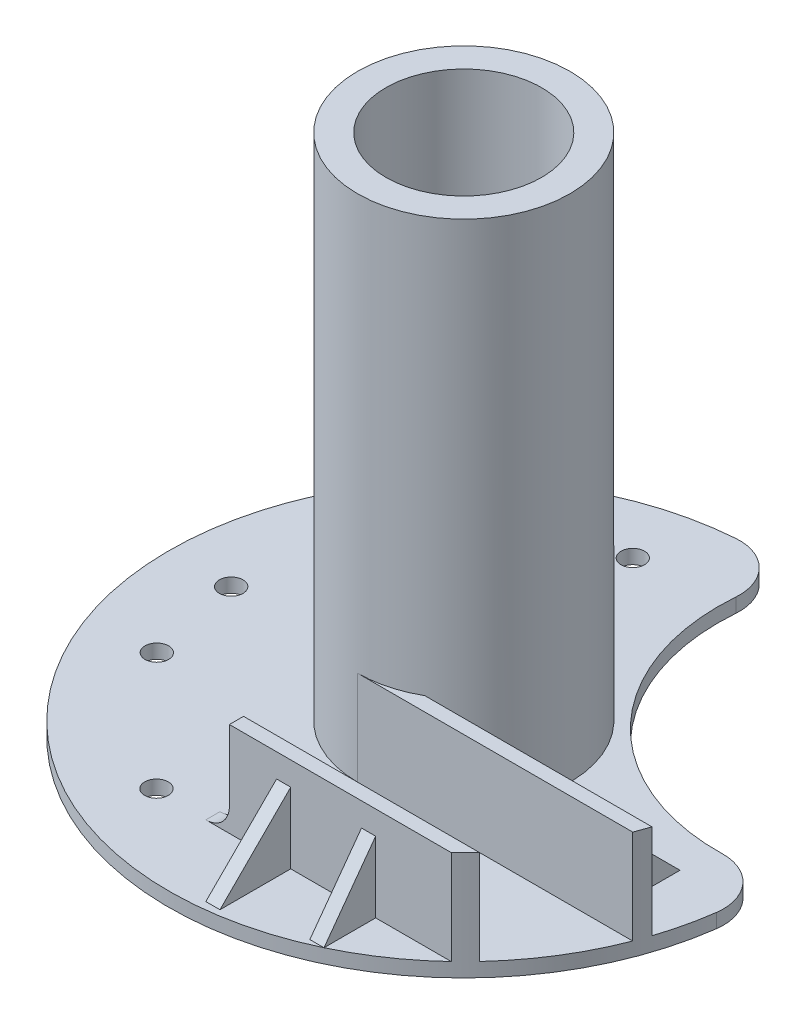
SolidWorks part; units mm, degrees
ref_plane "Front Plane" through (0, 0, 0) normal (0, 0, 1) x (1, 0, 0)
ref_plane "Top Plane" through (0, 0, 0) normal (0, 1, 0) x (1, 0, 0)
ref_plane "Right Plane" through (0, 0, 0) normal (1, 0, 0) x (0, 0, -1)
sketch "Sketch1" plane through (0, 0, 0) normal (0, 1, 0) x (1, 0, 0)
  circle A0 centre (0, 0) radius 22.5
  dimension "D1" = 45
extrude "Boss-Extrude1" add sketch "Sketch1" along normal blind 108
sketch "Sketch2" plane through (0, 0, 0) normal (0, 1, 0) x (1, 0, 0)
  circle A0 centre (0, 0) radius 62.5
  dimension "D1" = 125
extrude "Boss-Extrude2" add sketch "Sketch2" against normal blind 3
sketch "Sketch3" plane through (0, 0, 0) normal (0, 1, 0) x (1, 0, 0)
  circle A0 centre (0, 0) radius 16.5
  dimension "D1" = 33
extrude "Cut-Extrude1" cut sketch "Sketch3" along normal through all both and the other way through all
sketch "Sketch4" plane through (0, 0, 0) normal (0, 1, 0) x (1, 0, 0)
  line L0 (0, -22.5) -> (58.3095, -22.5)
  line L1 (59.3801, -19.5) -> (11.225, -19.5)
  line L2 (-4.1742, -42.5) -> (45.8258, -42.5)
  line L3 (-4.1742, -45.5) -> (42.8486, -45.5)
  line L4 (-4.1742, -42.5) -> (-4.1742, -45.5)
  arc A0 (0, -22.5) -> (11.225, -19.5) centre (0, 0) ccw
  circle A1 centre (0, 0) radius 62.5 construction
  arc A2 (42.8486, -45.5) -> (45.8258, -42.5) centre (0, 0) ccw
  arc A3 (58.3095, -22.5) -> (59.3801, -19.5) centre (0, 0) ccw
  dimension "D1" = 45
  dimension "D2" = 3
  dimension "D4" = 50
  dimension "D5" = 3
  dimension "D6" = 20
extrude "Boss-Extrude3" add sketch "Sketch4" along normal blind 20
chamfer "Chamfer1" distance 15 angle 45 2 edges at (35.3026, 0, 19.5) (19.3372, 0, 45.5)
sketch "Sketch5" plane through (0, 0, 0) normal (0, 1, 0) x (1, 0, 0)
  line L0 (11.225, -19.5) -> (29.3378, -19.5)
  line L1 (22.0454, -4.5) -> (29.3378, -4.5)
  line L2 (-4.1742, -45.5) -> (5.8258, -45.5)
  line L3 (-4.1742, -60.5) -> (5.8258, -60.5)
  line L4 (-4.1742, -45.5) -> (-4.1742, -60.5)
  line L5 (29.3378, -4.5) -> (29.3378, -19.5)
  line L6 (32.3378, -4.5) -> (32.3378, -19.5)
  line L7 (47.3378, -4.5) -> (47.3378, -19.5)
  line L8 (50.3378, -4.5) -> (50.3378, -19.5)
  line L9 (8.8258, -45.5) -> (8.8258, -60.5)
  line L10 (5.8258, -45.5) -> (5.8258, -60.5)
  line L11 (26.8258, -45.5) -> (26.8258, -56.4502)
  line L12 (23.8258, -45.5) -> (23.8258, -57.7805)
  line L13 (8.8258, -45.5) -> (23.8258, -45.5)
  line L14 (8.8258, -60.5) -> (15.6844, -60.5)
  line L15 (26.8258, -45.5) -> (42.8486, -45.5)
  line L16 (32.3378, -4.5) -> (47.3378, -4.5)
  line L17 (32.3378, -19.5) -> (47.3378, -19.5)
  line L18 (50.3378, -19.5) -> (59.3801, -19.5)
  line L19 (50.3378, -4.5) -> (62.3378, -4.5)
  arc A0 (15.6844, -60.5) -> (23.8258, -57.7805) centre (0, 0) ccw
  arc A2 (59.3801, -19.5) -> (62.3378, -4.5) centre (0, 0) ccw
  arc A4 (11.225, -19.5) -> (22.0454, -4.5) centre (0, 0) ccw
  arc A5 (26.8258, -56.4502) -> (42.8486, -45.5) centre (0, 0) ccw
  dimension "D1" = 125
  dimension "D2" = 45
  dimension "D3" = 19.5
  dimension "D4" = 4.5
  dimension "D5" = 45.5
  dimension "D6" = 60.5
  dimension "D7" = 4.1742
  dimension "D8" = 3
  dimension "D9" = 3
  dimension "D10" = 3
  dimension "D11" = 3
  dimension "D12" = 12
  dimension "D13" = 15
  dimension "D14" = 10
  dimension "D15" = 15
extrude "Cut-Extrude2" cut sketch "Sketch5" along normal through all
sketch "Sketch6" plane through (26.8258, 0, 0) normal (1, 0, 0) x (0, 0, -1)
  line L0 (-45.5, 15) -> (-56.4502, 0)
  line L3 (-45.5, 15) -> (-60.5, 0)
  line L5 (-60.5, 0) -> (-56.4502, 0)
  dimension "D1" = 45.5
  dimension "D2" = 15
  dimension "D3" = 56.4502
  dimension "D4" = 4.0498
  dimension "D5" = 18.5717
extrude "Cut-Extrude3" cut sketch "Sketch6" against normal blind 10
fillet "Fillet1" radius 5 1 edges at (-4.1742, 0, 44)
sketch "Sketch7" plane through (0, 0, 0) normal (0, 1, 0) x (1, 0, 0)
  circle A0 centre (50.9527, 47.9981) radius 45
  dimension "D1" = 90
  dimension "D2" = 70
extrude "Cut-Extrude4" cut sketch "Sketch7" against normal blind 249 contours A0
sketch "Sketch8" plane through (0, 0, 0) normal (0, 1, 0) x (1, 0, 0)
  circle A0 centre (-45.0574, -20) radius 2.5
  circle A1 centre (-49.2968, 0) radius 2.5
  circle A2 centre (-45.0574, 20) radius 2.5
  circle A3 centre (-34.7156, 35) radius 2.5
  circle A4 centre (-11.9937, 47.8155) radius 2.5
  circle A5 centre (-20.1289, -45) radius 2.5
  dimension "D1" = 5
other "AlignGroup1"
extrude "Cut-Extrude5" cut sketch "Sketch8" against normal blind 5
fillet "Fillet2" radius 10 2 edges at (8.1745, -1.5, -61.9631) (62.3405, -1.5, -4.4628)
